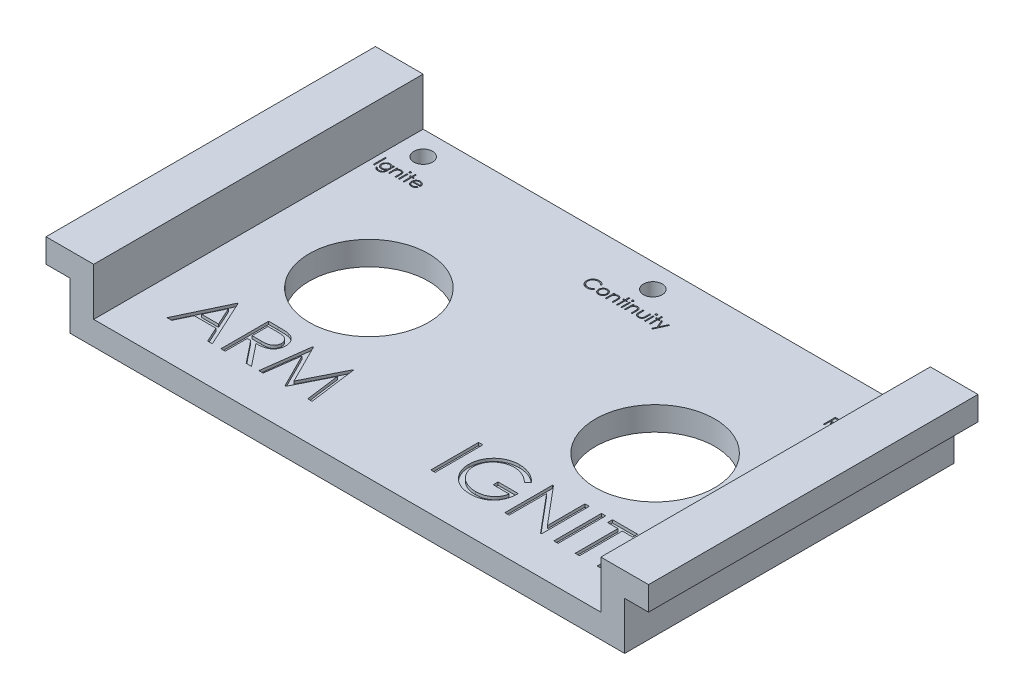
SolidWorks part; units mm, degrees
ref_plane "Front Plane" through (0, 0, 0) normal (0, 0, 1) x (1, 0, 0)
ref_plane "Top Plane" through (0, 0, 0) normal (0, 1, 0) x (1, 0, 0)
ref_plane "Right Plane" through (0, 0, 0) normal (1, 0, 0) x (0, 0, -1)
sketch "Çizim1" plane through (0, 0, 0) normal (0, 1, 0) x (1, 0, 0)
  line L1 (-73.85, -43.85) -> (73.85, -43.85)
  line L2 (-73.85, -43.85) -> (-73.85, 43.85)
  line L3 (-73.85, 43.85) -> (73.85, 43.85)
  line L4 (73.85, -43.85) -> (73.85, 43.85)
  line L5 (-73.85, -43.85) -> (73.85, 43.85) construction
  line L6 (-73.85, 43.85) -> (73.85, -43.85) construction
  point P0 (0, 0)
  dimension "D1" = 147.7
  dimension "D2" = 87.7
extrude "Yükseklik-Ekstrüzyon1" add sketch "Çizim1" along normal blind 6.35
sketch "Çizim2" plane through (-73.85, 0, 0) normal (-1, 0, 0) x (0, 0, 1)
  line L1 (-43.85, 6.35) -> (43.85, 6.35)
  line L2 (-43.85, 6.35) -> (-43.85, 19.05)
  line L3 (-43.85, 19.05) -> (43.85, 19.05)
  line L4 (43.85, 6.35) -> (43.85, 19.05)
  dimension "D1" = 87.7
  dimension "D2" = 12.7
extrude "Yükseklik-Ekstrüzyon2" add sketch "Çizim2" against normal blind 6.35
sketch "Çizim3" plane through (73.85, 0, 0) normal (1, 0, 0) x (0, 0, -1)
  line L1 (-43.85, 6.35) -> (43.85, 6.35)
  line L2 (-43.85, 6.35) -> (-43.85, 19.05)
  line L3 (-43.85, 19.05) -> (43.85, 19.05)
  line L4 (43.85, 6.35) -> (43.85, 19.05)
extrude "Yükseklik-Ekstrüzyon3" add sketch "Çizim3" against normal blind 6.35
sketch "Çizim4" plane through (73.85, 0, 0) normal (1, 0, 0) x (0, 0, -1)
  line L0 (43.85, 19.05) -> (43.85, 0) construction
  line L1 (-43.85, 19.05) -> (43.85, 19.05)
  line L2 (-43.85, 19.05) -> (-43.85, 12.7)
  line L3 (-43.85, 12.7) -> (43.85, 12.7)
  line L4 (43.85, 19.05) -> (43.85, 12.7)
  dimension "D1" = 6.35
sketch "Çizim6" plane through (-73.85, 0, 0) normal (-1, 0, 0) x (0, 0, 1)
  line L1 (-43.85, 19.05) -> (43.85, 19.05)
  line L2 (-43.85, 19.05) -> (-43.85, 12.7)
  line L3 (-43.85, 12.7) -> (43.85, 12.7)
  line L4 (43.85, 19.05) -> (43.85, 12.7)
extrude "Yükseklik-Ekstrüzyon4" add sketch "Çizim6" along normal blind 6.35
extrude "Yükseklik-Ekstrüzyon5" add sketch "Çizim4" along normal blind 6.35
sketch "Çizim7" plane through (0, 6.35, 0) normal (0, 1, 0) x (1, 0, 0)
  circle A0 centre (-38.1, 0) radius 15.875
  dimension "D1" = 31.75
  dimension "D2" = 38.1
extrude "Kes-Ekstrüzyon1" cut sketch "Çizim7" against normal blind 6.35
sketch "Çizim8" plane through (0, 6.35, 0) normal (0, 1, 0) x (1, 0, 0)
  circle A0 centre (38.1, 0) radius 15.875
  dimension "D1" = 31.75
  dimension "D2" = 38.1
extrude "Kes-Ekstrüzyon2" cut sketch "Çizim8" against normal blind 6.35
sketch "Çizim9" plane through (0, 6.35, 0) normal (0, 1, 0) x (1, 0, 0)
  line L0 (67.5, 43.85) -> (-67.5, 43.85) construction
  line L1 (67.5, 43.85) -> (67.5, -43.85) construction
  circle A0 centre (61.15, 37.5) radius 2.5
  dimension "D1" = 5
  dimension "D2" = 6.35
  dimension "D3" = 6.35
extrude "Kes-Ekstrüzyon3" cut sketch "Çizim9" against normal blind 6.35
sketch "Çizim10" plane through (0, 6.35, 0) normal (0, 1, 0) x (1, 0, 0)
  line L0 (67.5, 43.85) -> (-67.5, 43.85) construction
  circle A0 centre (0, 37.5) radius 2.5
  dimension "D1" = 5
  dimension "D2" = 6.35
extrude "Kes-Ekstrüzyon4" cut sketch "Çizim10" against normal blind 6.35
sketch "Çizim11" plane through (0, 6.35, 0) normal (0, 1, 0) x (1, 0, 0)
  line L0 (67.5, 43.85) -> (-67.5, 43.85) construction
  text T0 "Continuity"
  dimension "D1" = 14.732
extrude "Kes-Ekstrüzyon5" cut sketch "Çizim11" against normal blind 0.762
sketch "Çizim12" plane through (0, 6.35, 0) normal (0, 1, 0) x (1, 0, 0)
  line L0 (67.5, 43.85) -> (-67.5, 43.85) construction
  text T0 "Radio"
  dimension "D1" = 14.732
extrude "Kes-Ekstrüzyon6" cut sketch "Çizim12" against normal blind 0.762
sketch "Çizim13" plane through (0, 6.35, 0) normal (0, 1, 0) x (1, 0, 0)
  line L0 (-67.5, -43.85) -> (67.5, -43.85) construction
  text T0 "ARM" font "Century Gothic" height 12.7
  dimension "D1" = 10.16
sketch "Çizim14" plane through (0, 6.35, 0) normal (0, 1, 0) x (1, 0, 0)
  line L0 (-67.5, -43.85) -> (67.5, -43.85) construction
  text T0 "IGNITE" font "Century Gothic" height 12.7
  dimension "D1" = 10.16
extrude "Kes-Ekstrüzyon7" cut sketch "Çizim13" against normal blind 0.762
extrude "Kes-Ekstrüzyon8" cut sketch "Çizim14" against normal blind 0.762
sketch "Çizim15" plane through (0, 6.35, 0) normal (0, 1, 0) x (1, 0, 0)
  line L0 (67.5, 43.85) -> (-67.5, 43.85) construction
  line L1 (-67.5, -43.85) -> (-67.5, 43.85) construction
  circle A0 centre (-61.15, 37.5) radius 2.5
  dimension "D1" = 5
  dimension "D2" = 6.35
  dimension "D3" = 6.35
extrude "Kes-Ekstrüzyon9" cut sketch "Çizim15" against normal blind 6.35
sketch "Çizim16" plane through (0, 6.35, 0) normal (0, 1, 0) x (1, 0, 0)
  line L0 (67.5, 43.85) -> (-67.5, 43.85) construction
  text T0 "Ignite"
  dimension "D1" = 14.732
extrude "Kes-Ekstrüzyon10" cut sketch "Çizim16" against normal blind 0.762
